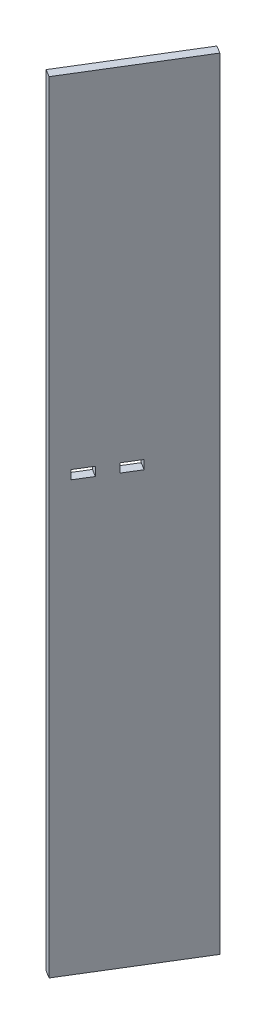
SolidWorks part; units mm, degrees
ref_plane "Front Plane" through (0, 0, 0) normal (0, 0, 1) x (1, 0, 0)
ref_plane "Top Plane" through (0, 0, 0) normal (0, 1, 0) x (1, 0, 0)
ref_plane "Right Plane" through (0, 0, 0) normal (1, 0, 0) x (0, 0, -1)
sketch "Sketch2" plane through (-119.8987, 0, -90.0076) normal (0, 1, 0) x (-0.8523, 0, -0.523)
  line L1 (-38.1, -44.45) -> (-44.45, -44.45)
  line L2 (-38.1, -44.45) -> (-38.1, 44.45)
  line L3 (-38.1, 44.45) -> (-44.45, 44.45)
  line L4 (-44.45, -44.45) -> (-44.45, 44.45)
  dimension "D1" = 6.35
  dimension "D2" = 88.9
extrude "Boss-Extrude1" add sketch "Sketch2" along normal blind 558.8
sketch "Sketch3" plane through (-89.338, 0, -54.8228) normal (0.8523, 0, 0.523) x (0.523, 0, -0.8523)
  line L1 (-19.05, 313.305) -> (-6.35, 313.305)
  line L2 (-19.05, 313.305) -> (-19.05, 306.955)
  line L3 (-19.05, 306.955) -> (-6.35, 306.955)
  line L4 (-6.35, 313.305) -> (-6.35, 306.955)
  line L5 (6.35, 313.305) -> (19.05, 313.305)
  line L6 (6.35, 313.305) -> (6.35, 306.955)
  line L7 (6.35, 306.955) -> (19.05, 306.955)
  line L8 (19.05, 313.305) -> (19.05, 306.955)
  line L10 (0, 310.13) -> (38.2669, 310.13) construction
  line L11 (-25.2474, 306.955) -> (48.5256, 306.955) construction
  dimension "D1" = 12.7
  dimension "D2" = 6.35
  dimension "D3" = 6.35
  dimension "D4" = 12.7
  dimension "D5" = 12.7
extrude "Cut-Extrude1" cut sketch "Sketch3" against normal through all
